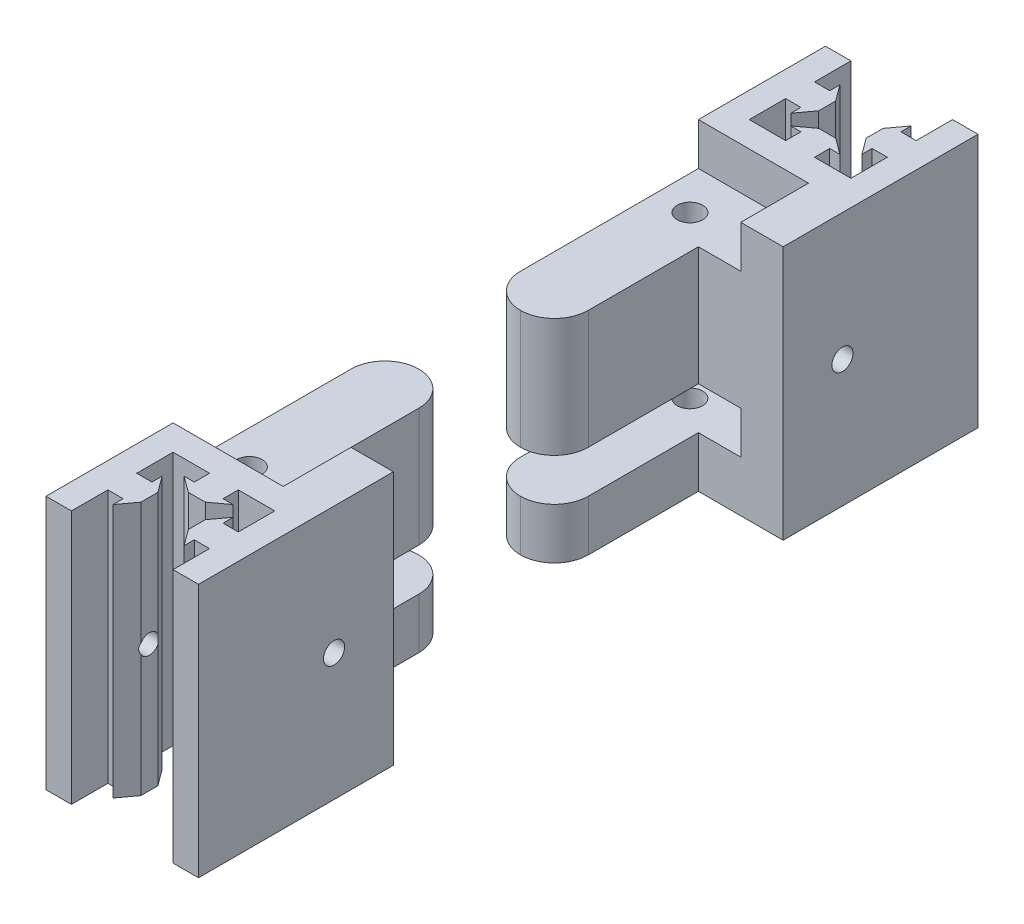
SolidWorks part; units mm, degrees
ref_plane "Plan de face" through (0, 0, 0) normal (0, 0, 1) x (1, 0, 0)
ref_plane "Plan de dessus" through (0, 0, 0) normal (0, 1, 0) x (1, 0, 0)
ref_plane "Plan de droite" through (0, 0, 0) normal (1, 0, 0) x (0, 0, -1)
ref_axis "Axe1" through (0, 17.691, 0) along (0, -1, 0)
ref_axis "Axe2" through (23.7847, 0, 0) along (-1, 0, 0)
ref_axis "Axe3" through (0, 0, -21.7718) along (0, 0, 1)
sketch "Esquisse8" plane through (0, 0, 0) normal (0, 1, 0) x (1, 0, 0)
  line L0 (-6, 1.7) -> (-4.2, 1.7)
  line L1 (0, -16.9042) -> (0, 16.9042) construction
  line L2 (-4.2, 1.7) -> (-4.2, 2.9)
  line L3 (-4.2, 2.9) -> (-2.8, 1)
  line L4 (-2.8, 1) -> (-2.8, -1)
  line L5 (-2.8, -1) -> (-4.2, -2.9)
  line L6 (-4.2, -2.9) -> (-4.2, -1.7)
  line L7 (-4.2, -1.7) -> (-6, -1.7)
  line L8 (-6, -1.7) -> (-6, -9)
  line L9 (-6, -9) -> (-9, -9)
  line L10 (-9, -9) -> (-9, 9)
  line L11 (-9, 9) -> (-6, 9)
  line L12 (-6, 9) -> (-6, 1.7)
  line L16 (23.7847, 0) -> (-17.9556, 0) construction
  point P14 (-2.8, 0)
  dimension "D1" = 1.8
  dimension "D2" = 3.2
  dimension "D3" = 18
  dimension "D4" = 2
  dimension "D5" = 1.2
  dimension "D7" = 3
  dimension "D8" = 3.4
  dimension "D9" = 6
extrude "Boss.-Extru.6" add sketch "Esquisse8" along normal mid plane 30 separate body
pattern_circular "Répétition circulaire3" count 3 every 90 about axis through (0, 17.691, 0) along (0, -1, 0) of bodies 117
sketch "Esquisse9" plane through (0, 15, 0) normal (0, 1, 0) x (1, 0, 0)
  line L0 (9, -9) -> (9, 9) construction
  line L1 (-9, -9) -> (9, -9)
  line L2 (-9, -9) -> (-9, -6)
  line L3 (-9, -6) -> (9, -6)
  line L4 (9, -9) -> (9, -6)
  dimension "D1" = 3
extrude "Enlèv. mat.-Extru.1" cut sketch "Esquisse9" against normal through all
sketch "Esquisse10" plane through (0, 0, -9) normal (0, 0, -1) x (-1, 0, 0)
  line L1 (9, 10) -> (1, 10)
  line L2 (9, 10) -> (9, -4)
  line L3 (9, -4) -> (1, -4)
  line L4 (1, 10) -> (1, -4)
  line L5 (1, -9) -> (9, -9)
  line L6 (9, 15) -> (9, -15) construction
  line L7 (-9, 15) -> (9, 15) construction
  line L8 (1, -9) -> (1, -15)
  line L9 (1, -15) -> (9, -15)
  line L10 (9, -9) -> (9, -15)
  dimension "D1" = 8
  dimension "D2" = 5
  dimension "D3" = 5
  dimension "D4" = 14
  dimension "D5" = 6
extrude "Boss.-Extru.7" add sketch "Esquisse10" along normal blind 25
sketch "Esquisse12" plane through (0, 0, -9) normal (0, 0, -1) x (-1, 0, 0)
  line L0 (9, -9) -> (1, -9) construction
  line L1 (-9, 15) -> (-9, -15) construction
  line L2 (-9, -15) -> (1, -15)
  line L3 (-9, -15) -> (-9, -9)
  line L4 (-9, -9) -> (1, -9)
  line L5 (1, -15) -> (1, -9)
  line L6 (-9, -15) -> (1, -15) construction
  line L8 (1, -9) -> (1, -15) construction
  line L9 (9, 10) -> (1, 10) construction
  line L10 (-9, 10) -> (1, 10)
  line L11 (-9, 10) -> (-9, -4)
  line L12 (-9, -4) -> (1, -4)
  line L13 (1, 10) -> (1, -4)
extrude "Boss.-Extru.8" add sketch "Esquisse12" along normal blind 8
fillet "Congé1" radius 4 4 edges at (-9, 3, -34) (-1, -12, -34) (-9, -12, -34) (-1, 3, -34)
sketch "Esquisse11" plane through (0, 15, 0) normal (0, 1, 0) x (1, 0, 0)
  line L0 (-9, 9) -> (-9, -6) construction
  line L1 (9, 9) -> (-9, 9) construction
  circle A0 centre (-5, 14) radius 1.5
  dimension "D3" = 3
  dimension "D2" = 4
  dimension "D4" = 5
extrude "Enlèv. mat.-Extru.2" cut sketch "Esquisse11" against normal through all
sketch "Esquisse13" plane through (0, 0, -9) normal (0, 0, -1) x (-1, 0, 0)
  line L0 (-9, -15) -> (1, -15) construction
  line L1 (-9, 15) -> (-4, 15)
  line L2 (-9, 15) -> (-9, -15)
  line L3 (-9, -15) -> (-4, -15)
  line L4 (-4, 15) -> (-4, -15)
  dimension "D1" = 5
extrude "Boss.-Extru.9" add sketch "Esquisse13" along normal up to surface (8 mm away) up to face at (4, -12, -17)
sketch "Esquisse16" plane through (9, 0, 0) normal (1, 0, 0) x (0, 0, -1)
  line L0 (15.0486, 0) -> (-15.0486, 0) construction
  line L1 (0, 20.8701) -> (0, -20.8701) construction
  circle A0 centre (10, 0) radius 1.25
  dimension "D1" = 10
  dimension "D2" = 2.5
extrude "Enlèv. mat.-Extru.3" cut sketch "Esquisse16" against normal through all
sketch "Esquisse17" plane through (-9, 0, 0) normal (-1, 0, 0) x (0, 0, 1)
  line L0 (0, -20.8701) -> (0, 20.8701) construction
  circle A0 centre (0, 0) radius 1.15
  dimension "D1" = 2.3
extrude "Enlèv. mat.-Extru.4" cut sketch "Esquisse17" against normal up to next
ref_plane "Plan de symétrie" through (0, 0, -40) normal (0, 0, 1) x (1, 0, 0)
mirror "Symétrie2" about plane through (0, 0, -40) normal (0, 0, 1) of bodies 153
